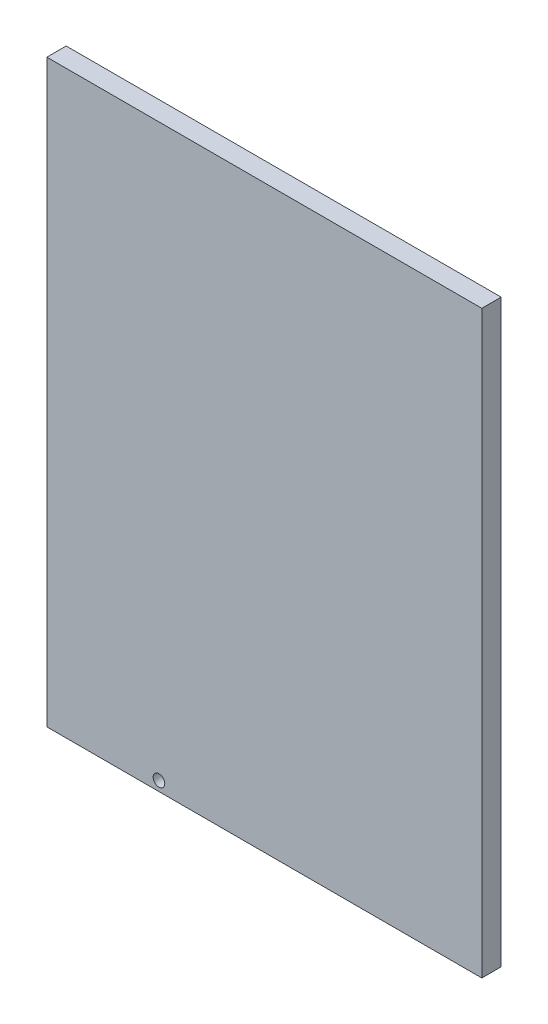
SolidWorks part; units mm, degrees
ref_plane "Front Plane" through (0, 0, 0) normal (0, 0, 1) x (1, 0, 0)
ref_plane "Top Plane" through (0, 0, 0) normal (0, 1, 0) x (1, 0, 0)
ref_plane "Right Plane" through (0, 0, 0) normal (1, 0, 0) x (0, 0, -1)
sketch "Sketch1" plane through (0, 0, 0) normal (0, 0, 1) x (1, 0, 0)
  line L1 (-112.5, -150) -> (112.5, -150)
  line L2 (-112.5, -150) -> (-112.5, 150)
  line L3 (-112.5, 150) -> (112.5, 150)
  line L4 (112.5, -150) -> (112.5, 150)
  line L5 (-112.5, -150) -> (112.5, 150) construction
  line L6 (-112.5, 150) -> (112.5, -150) construction
  point P0 (0, 0)
  dimension "D1" = 225
  dimension "D2" = 300
extrude "Boss-Extrude1" add sketch "Sketch1" along normal blind 10
sketch "Sketch2" plane through (0, 0, 10) normal (0, 0, 1) x (1, 0, 0)
  line L0 (-112.5, 150) -> (-112.5, -150) construction
  line L1 (-112.5, -150) -> (112.5, -150) construction
  circle A0 centre (-54.5, -145) radius 3
  dimension "D1" = 6
  dimension "D2" = 58
  dimension "D3" = 5
extrude "Cut-Extrude4" cut sketch "Sketch2" against normal through all
equation "\"PCWidth\"= 172mm"
equation "\"PCLength\"= 320mm"
equation "\"PCHeight\"= 242mm"
equation "\"WallThickness\"= 10mm"
equation "\"ThermoBarrierThickness\"= 3mm"
equation "\"HotSideGap\"= 50mm"
equation "\"PCClearance\"= 25mm"
equation "\"D2@Sketch1\"=\"RadiatorHeight\" + \"PCClearance\""
equation "\"D1@Sketch1\"=\"PCWidth\" + \"ThermoBarrierThickness\" + \"HotSideGap\""
equation "\"D1@Boss-Extrude1\"=\"WallThickness\""
equation "\"RadiatorHeight\"= 275mm"
equation "\"D2@Sketch2\"=\"HotSideGap\" + \"ThermoBarrierThickness\" + 5"
